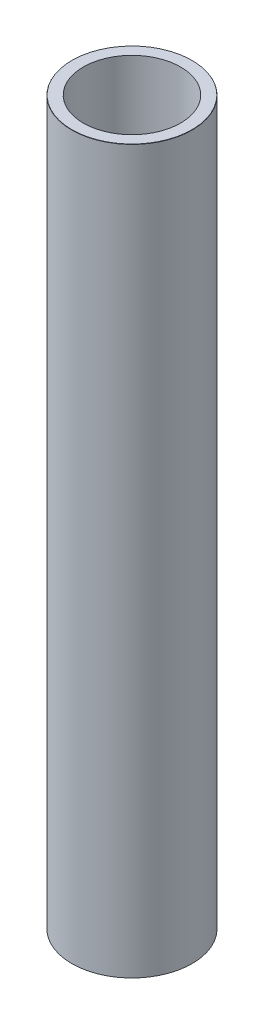
SolidWorks part; units mm, degrees
ref_plane "Front Plane" through (0, 0, 0) normal (0, 0, 1) x (1, 0, 0)
ref_plane "Top Plane" through (0, 0, 0) normal (0, 1, 0) x (1, 0, 0)
ref_plane "Right Plane" through (0, 0, 0) normal (1, 0, 0) x (0, 0, -1)
sketch "Sketch1" plane through (0, 0, 0) normal (0, 1, 0) x (1, 0, 0)
  circle A0 centre (0, 0) radius 50
  dimension "SHAFT_OD" = 100
extrude "Boss-Extrude1" add sketch "Sketch1" along normal blind 600
sketch "Sketch2" plane through (0, 0, 0) normal (0, 1, 0) x (1, 0, 0)
  circle A0 centre (0, 0) radius 40.4138
  dimension "BORE_D" = 80.8275
extrude "Cut-Extrude1" cut sketch "Sketch2" along normal through all
chamfer "Chamfer1" distance 0.2011 angle 30 2 edges at (0, 600, 50) (0, 0, 50) first distance on face at (0, 600, 50) first distance on face at (0, 0, 40.4138)
